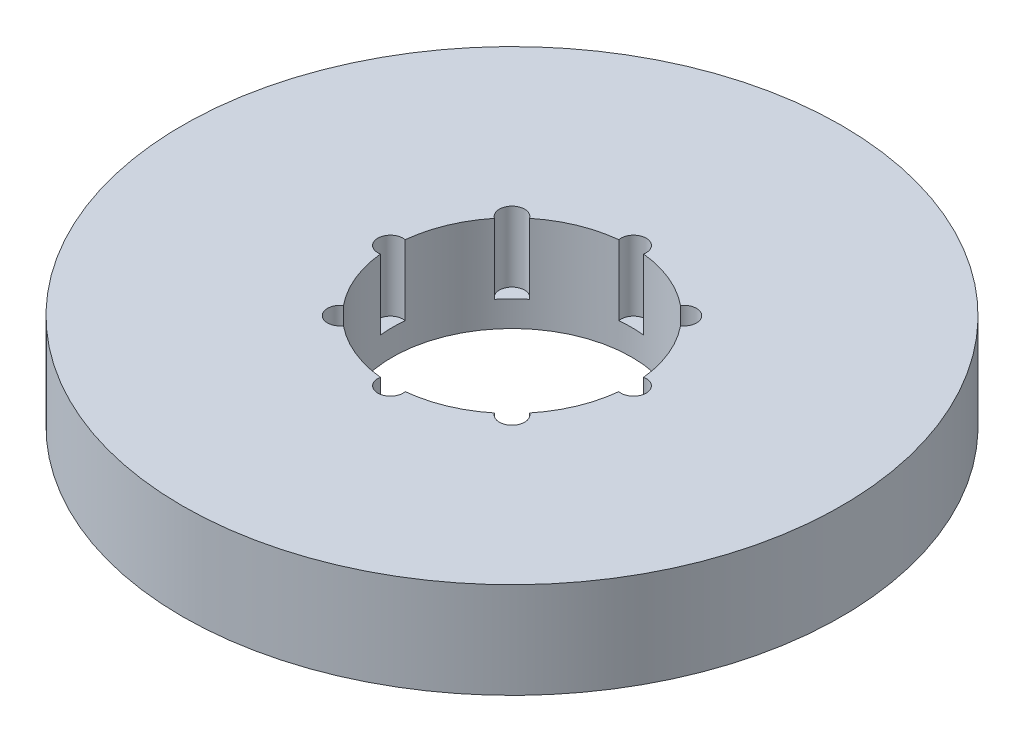
SolidWorks part; units mm, degrees
ref_plane "Front Plane" through (0, 0, 0) normal (0, 0, 1) x (1, 0, 0)
ref_plane "Top Plane" through (0, 0, 0) normal (0, 1, 0) x (1, 0, 0)
ref_plane "Right Plane" through (0, 0, 0) normal (1, 0, 0) x (0, 0, -1)
sketch "Sketch1" plane through (0, 0, 0) normal (0, 1, 0) x (1, 0, 0)
  circle A0 centre (0, 0) radius 82.5
  dimension "FLANGE_OD" = 165
extrude "Boss-Extrude1" add sketch "Sketch1" along normal blind 24
sketch "Sketch2" plane through (0, 0, 0) normal (0, 1, 0) x (1, 0, 0)
  circle A0 centre (0, 0) radius 30
  dimension "BORE_D" = 60
extrude "Cut-Extrude1" cut sketch "Sketch2" along normal through all
sketch "Sketch3" plane through (0, 24, 0) normal (0, 1, 0) x (1, 0, 0)
  circle A0 centre (0, 0) radius 30.4287 construction
  circle A1 centre (-30.4287, 0) radius 3.1639
  dimension "BOLT_D" = 6.3278
  dimension "BOLT_PCD" = 60.8574
extrude "Cut-Extrude2" cut sketch "Sketch3" against normal blind 17.5621
pattern_circular "CirPattern1" count 8 over 360 about axis through (0, 0, 0) along (0, 1, 0) of "Cut-Extrude2"
